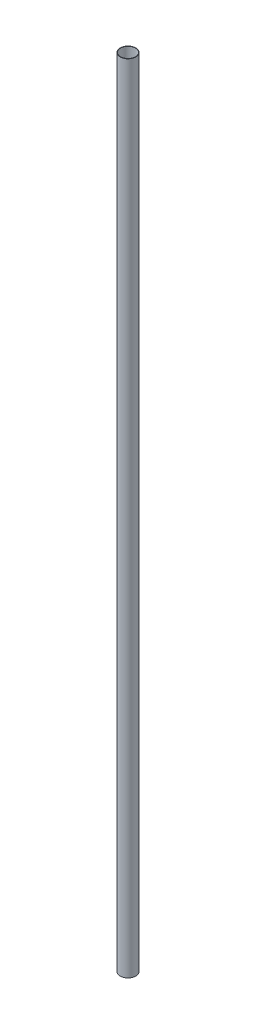
SolidWorks part; units mm, degrees
ref_plane "Front Plane" through (0, 0, 0) normal (0, 0, 1) x (1, 0, 0)
ref_plane "Top Plane" through (0, 0, 0) normal (0, 1, 0) x (1, 0, 0)
ref_plane "Right Plane" through (0, 0, 0) normal (1, 0, 0) x (0, 0, -1)
sketch "Sketch2" plane through (0, 0, 0) normal (0, 1, 0) x (1, 0, 0)
  circle A0 centre (0, 0) radius 9.525
  circle A1 centre (0, 0) radius 10.033
  dimension "D1" = 19.05
  dimension "D2" = 20.066
extrude "Boss-Extrude1" add sketch "Sketch2" along normal blind 1016
